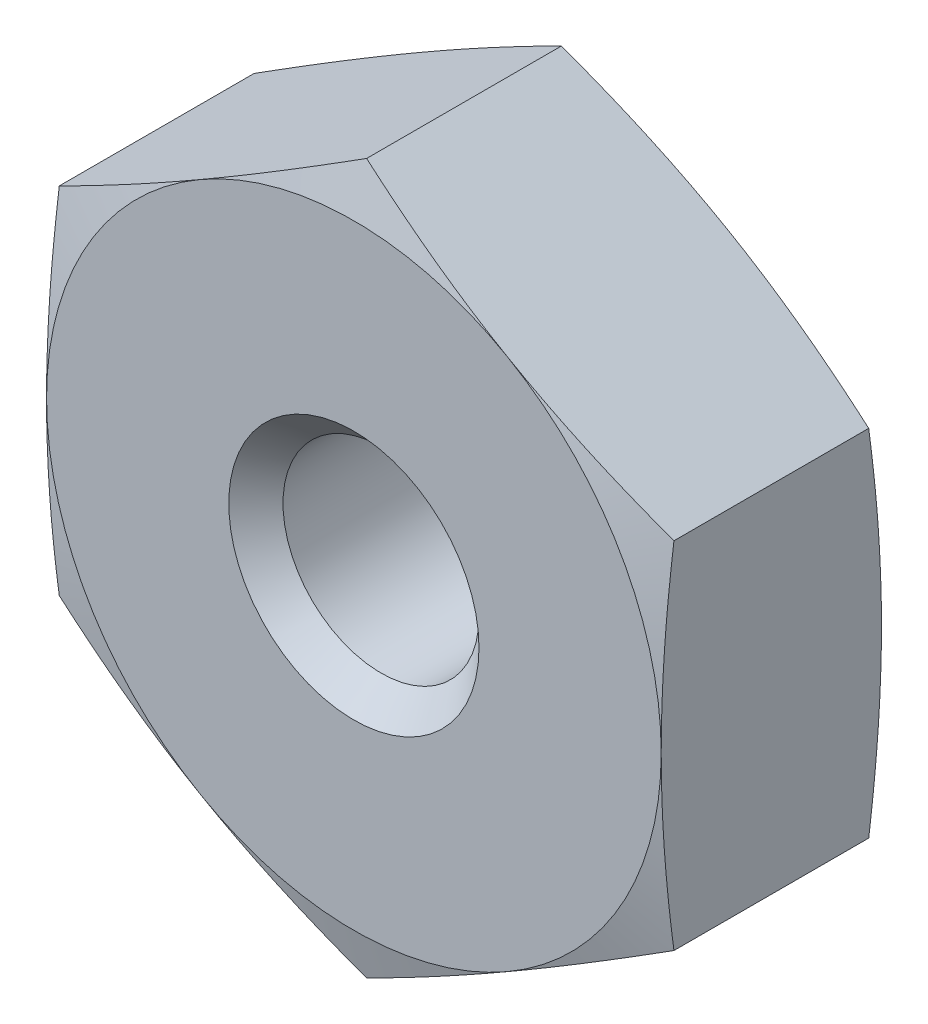
SolidWorks part; units mm, degrees
ref_plane "Front Plane" through (0, 0, 0) normal (0, 0, 1) x (1, 0, 0)
ref_plane "Top Plane" through (0, 0, 0) normal (0, 1, 0) x (1, 0, 0)
ref_plane "Right Plane" through (0, 0, 0) normal (1, 0, 0) x (0, 0, -1)
sketch "Sketch1" plane through (0, 0, 0) normal (1, 0, 0) x (0, 0, -1)
  line L0 (0, 0) -> (0, 3.8989)
  line L1 (0, 3.8989) -> (0.2089, 4.6787)
  line L2 (0.2089, 4.6787) -> (2.5851, 4.6787)
  line L3 (2.5851, 4.6787) -> (2.794, 3.8989)
  line L4 (2.794, 3.8989) -> (2.794, 0)
  line L5 (2.794, 0) -> (0, 0)
  line L6 (2.794, 0) -> (0, 0) construction
sketch "Sketch2" plane through (0, 0, 0) normal (0, 0, 1) x (1, 0, 0)
  line L0 (-7.7978, -7.7978) -> (7.7978, -7.7978)
  line L1 (7.7978, -7.7978) -> (7.7978, 7.7978)
  line L2 (7.7978, 7.7978) -> (-7.7978, 7.7978)
  line L3 (-7.7978, 7.7978) -> (-7.7978, -7.7978)
  line L4 (-3.8989, -2.251) -> (0, -4.5021)
  line L5 (0, -4.5021) -> (3.8989, -2.251)
  line L6 (3.8989, -2.251) -> (3.8989, 2.251)
  line L7 (3.8989, 2.251) -> (0, 4.5021)
  line L8 (0, 4.5021) -> (-3.8989, 2.251)
  line L9 (-3.8989, 2.251) -> (-3.8989, -2.251)
revolve "Revolve1" add sketch "Sketch1" angle 360 about L6 reverse direction yes
extrude "Cut-Extrude1" cut sketch "Sketch2" against normal blind 2.794
sketch "Sketch3" plane through (0, 0, 0) normal (1, 0, 0) x (0, 0, -1)
  line L0 (0, 0) -> (0, 1.5875)
  line L1 (0, 1.5875) -> (0.3442, 1.2433)
  line L2 (0.3442, 1.2433) -> (2.4498, 1.2433)
  line L3 (2.4498, 1.2433) -> (2.794, 1.5875)
  line L4 (2.794, 1.5875) -> (2.794, 0)
  line L5 (2.794, 0) -> (0, 0)
  line L6 (2.794, 0) -> (0, 0) construction
revolve "Cut-Revolve1" cut sketch "Sketch3" angle 360 about L6 reverse direction yes
cosmetic thread "Cosmetic Thread1" parameters "D1"=2.794, "D2"=3.175
ref_plane "NUT XY" through (0, 0, 0) normal (0, 0, 1) x (1, 0, 0)
ref_plane "NUT XZ" through (0, 0, 0) normal (0, -1, 0) x (-1, 0, 0)
ref_plane "NUT YZ" through (0, 0, 0) normal (1, 0, 0) x (0, 0, -1)
ref_axis "NUT X" through (-80.9, 0, 0) along (1, 0, 0)
ref_axis "NUT Y" through (0, -50, 0) along (0, 1, 0)
ref_axis "NUT Z" through (0, 0, 80.9) along (0, 0, -1)
sketch3d "NUT"
  point P0 (0, 0, 0)
ref_plane "a1 XY" through (0, 0, 0) normal (0, 0, 1) x (1, 0, 0)
ref_plane "a1 XZ" through (0, 3.8989, 0) normal (0, -1, 0) x (-1, 0, 0)
ref_plane "a1 YZ" through (-3.8989, 0, 0) normal (1, 0, 0) x (0, 0, -1)
ref_axis "a1 X" through (-80.9, 3.8989, 0) along (1, 0, 0)
ref_axis "a1 Y" through (-3.8989, -50, 0) along (0, 1, 0)
ref_axis "a1 Z" through (-3.8989, 3.8989, 80.9) along (0, 0, -1)
sketch3d "a1"
  point P0 (-3.8989, 3.8989, 0)
ref_plane "a2 XY" through (0, 0, 0) normal (0, 0, 1) x (1, 0, 0)
ref_plane "a2 XZ" through (0, 3.8989, 0) normal (0, -1, 0) x (-1, 0, 0)
ref_plane "a2 YZ" through (3.8989, 0, 0) normal (1, 0, 0) x (0, 0, -1)
ref_axis "a2 X" through (-80.9, 3.8989, 0) along (1, 0, 0)
ref_axis "a2 Y" through (3.8989, -50, 0) along (0, 1, 0)
ref_axis "a2 Z" through (3.8989, 3.8989, 80.9) along (0, 0, -1)
sketch3d "a2"
  point P0 (3.8989, 3.8989, 0)
ref_plane "b1 XY" through (0, 0, 0) normal (1, 0, 0) x (0, 0, -1)
ref_plane "b1 XZ" through (0, 3.8989, 0) normal (0, -1, 0) x (-1, 0, 0)
ref_plane "b1 YZ" through (0, 0, 0) normal (0, 0, -1) x (-1, 0, 0)
ref_axis "b1 X" through (0, 3.8989, 80.9) along (0, 0, -1)
ref_axis "b1 Y" through (0, -50, 0) along (0, 1, 0)
ref_axis "b1 Z" through (80.9, 3.8989, 0) along (-1, 0, 0)
sketch3d "b1"
  point P0 (0, 3.8989, 0)
ref_plane "b2 XY" through (0, 0, 0) normal (1, 0, 0) x (0, 0, -1)
ref_plane "b2 XZ" through (0, 3.8989, 0) normal (0, -1, 0) x (-1, 0, 0)
ref_plane "b2 YZ" through (0, 0, -2.794) normal (0, 0, -1) x (-1, 0, 0)
ref_axis "b2 X" through (0, 3.8989, 80.9) along (0, 0, -1)
ref_axis "b2 Y" through (0, -50, -2.794) along (0, 1, 0)
ref_axis "b2 Z" through (80.9, 3.8989, -2.794) along (-1, 0, 0)
sketch3d "b2"
  point P0 (0, 3.8989, -2.794)
ref_plane "e XY" through (0, 0, 0) normal (1, 0, 0) x (0, 0, -1)
ref_plane "e XZ" through (0, 0, 0) normal (0, -1, 0) x (-1, 0, 0)
ref_plane "e YZ" through (0, 0, -2.794) normal (0, 0, -1) x (-1, 0, 0)
ref_axis "e X" through (0, 0, 80.9) along (0, 0, -1)
ref_axis "e Y" through (0, -50, -2.794) along (0, 1, 0)
ref_axis "e Z" through (80.9, 0, -2.794) along (-1, 0, 0)
sketch3d "e"
  point P0 (0, 0, -2.794)
ref_plane "ol1 XY" through (0, 0, 0) normal (0, 1, 0) x (1, 0, 0)
ref_plane "ol1 XZ" through (0, 0, -3.8989) normal (0, 0, 1) x (1, 0, 0)
ref_plane "ol1 YZ" through (0, 0, 0) normal (1, 0, 0) x (0, 0, -1)
ref_axis "ol1 X" through (-80.9, 0, -3.8989) along (1, 0, 0)
ref_axis "ol1 Y" through (0, 0, 50) along (0, 0, -1)
ref_axis "ol1 Z" through (0, 50, -3.8989) along (0, -1, 0)
sketch3d "ol1"
  point P0 (0, 0, -3.8989)
ref_plane "ol2 XY" through (0, 0, 0) normal (0, 1, 0) x (1, 0, 0)
ref_plane "ol2 XZ" through (0, 0, -3.8989) normal (0, 0, 1) x (1, 0, 0)
ref_plane "ol2 YZ" through (2.794, 0, 0) normal (1, 0, 0) x (0, 0, -1)
ref_axis "ol2 X" through (-80.9, 0, -3.8989) along (1, 0, 0)
ref_axis "ol2 Y" through (2.794, 0, 50) along (0, 0, -1)
ref_axis "ol2 Z" through (2.794, 50, -3.8989) along (0, -1, 0)
sketch3d "ol2"
  point P0 (2.794, 0, -3.8989)
ref_plane "th1 XY" through (0, 0, 0) normal (1, 0, 0) x (0, 0, -1)
ref_plane "th1 XZ" through (0, 1.5875, 0) normal (0, -1, 0) x (-1, 0, 0)
ref_plane "th1 YZ" through (0, 0, -2.794) normal (0, 0, -1) x (-1, 0, 0)
ref_axis "th1 X" through (0, 1.5875, 80.9) along (0, 0, -1)
ref_axis "th1 Y" through (0, -50, -2.794) along (0, 1, 0)
ref_axis "th1 Z" through (80.9, 1.5875, -2.794) along (-1, 0, 0)
sketch3d "th1"
  point P0 (0, 1.5875, -2.794)
ref_plane "th2 XY" through (0, 0, 0) normal (1, 0, 0) x (0, 0, -1)
ref_plane "th2 XZ" through (0, -1.5875, 0) normal (0, -1, 0) x (-1, 0, 0)
ref_plane "th2 YZ" through (0, 0, -2.794) normal (0, 0, -1) x (-1, 0, 0)
ref_axis "th2 X" through (0, -1.5875, 80.9) along (0, 0, -1)
ref_axis "th2 Y" through (0, -50, -2.794) along (0, 1, 0)
ref_axis "th2 Z" through (80.9, -1.5875, -2.794) along (-1, 0, 0)
sketch3d "th2"
  point P0 (0, -1.5875, -2.794)
